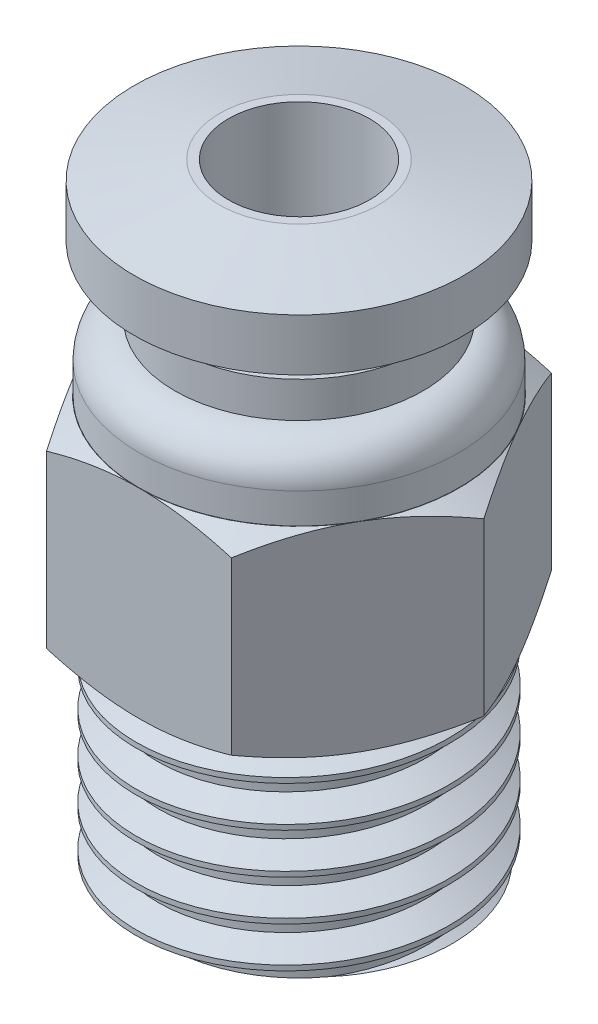
SolidWorks part; units mm, degrees
ref_plane "前视基准面" through (0, 0, 0) normal (0, 0, 1) x (1, 0, 0)
ref_plane "上视基准面" through (0, 0, 0) normal (0, 1, 0) x (1, 0, 0)
ref_plane "右视基准面" through (0, 0, 0) normal (1, 0, 0) x (0, 0, -1)
sketch "草图1" plane through (0, 0, 0) normal (0, 0, 1) x (1, 0, 0)
  line L0 (0, 0) -> (0, 6.9663) construction
  line L1 (-3.25, -7.6125) -> (-3.25, -4.0125)
  line L5 (-2.6208, 8.1221) -> (-3.82, 8.1221)
  line L6 (-3.82, 8.1221) -> (-3.82, 7.0221)
  line L7 (-3.82, 7.0221) -> (-4.92, 7.0221)
  line L8 (-4.92, 7.0221) -> (-4.92, 4.9875)
  line L9 (-4.92, 4.9875) -> (-5.69, 4.9875)
  line L10 (-5.69, 4.9875) -> (-5.69, -1.6125)
  line L11 (-5.69, -1.6125) -> (-4.14, -1.6125)
  line L12 (-4.14, -1.6125) -> (-4.14, -7.6125)
  line L13 (-4.14, -7.6125) -> (-3.25, -7.6125)
  line L14 (-2.6208, 8.1221) -> (-2.6208, 9.1221)
  line L15 (-2.6208, 9.1221) -> (-5.07, 9.1221)
  line L16 (-5.07, 9.1221) -> (-5.07, 10.7221)
  line L17 (-5.07, 10.7221) -> (-2.445, 11.2875)
  line L18 (-2.445, 11.2875) -> (-2.17, 11.2875)
  line L19 (-2.17, 11.2875) -> (-2.17, -3.2452)
  line L20 (-2.17, -3.2452) -> (-3.25, -4.0125)
  dimension "D1" = 18.9
  dimension "D2" = 8.28
  dimension "D3" = 5.69
  dimension "D4" = 3.25
  dimension "D5" = 3.6
  dimension "D6" = 2.17
  dimension "D7" = 5.07
  dimension "D8" = 1.6
  dimension "D9" = 1
  dimension "D10" = 3.82
  dimension "D11" = 2.1
  dimension "D12" = 4.92
  dimension "D13" = 6.6
  dimension "D14" = 6
revolve "旋转1" add sketch "草图1" angle 360 about L0
fillet "圆角1" radius 1.1 1 edges at (0, 7.0221, -4.92)
chamfer "倒角1" distance 0.76 angle 30 1 edges at (0, 4.9875, -5.69)
chamfer "倒角3" distance 0.9 distance2 1.55 1 edges at (0, -1.6125, -5.69)
ref_plane "基准面1" through (0, 4.5487, 0) normal (0, 1, 0) x (1, 0, 0)
sketch "草图3" plane through (0, 4.5487, 0) normal (0, 1, 0) x (1, 0, 0)
  line L1 (-5.69, 0) -> (-2.845, -4.9277)
  line L2 (-2.845, -4.9277) -> (2.845, -4.9277)
  line L3 (2.845, -4.9277) -> (5.69, 0)
  line L4 (5.69, 0) -> (2.845, 4.9277)
  line L5 (2.845, 4.9277) -> (-2.845, 4.9277)
  line L6 (-2.845, 4.9277) -> (-5.69, 0)
  circle A0 centre (0, 0) radius 4.9277 construction
  circle A1 centre (0, 0) radius 6.1809
extrude "切除-拉伸1" cut sketch "草图3" against normal blind 7 and the other way blind 2
thread "螺纹线1" pitch 1.25 start angle 0, offset 1, length 0, pitch 1.25, diameter 8.28
ref_plane "基准面2" through (-4.14, -0.6125, 0) normal (0, 0, 1) x (-1, 0, 0)
sketch "螺纹线轮廓1" plane through (-4.14, -0.6125, 0) normal (0, 0, 1) x (-1, 0, 0)
  line L0 (0, 0) -> (0, 1.25) construction
  line L1 (0, 0) -> (0.6766, 0.3906)
  line L2 (0.6766, 0.3906) -> (0.6766, 0.5469)
  line L3 (0.6766, 0.5469) -> (0, 0.9375)
  line L4 (0.6766, 0.4687) -> (0, 0.4687) construction
  line L11 (0, 0) -> (0, 0.9375)
  point P2 (0, 0)
  dimension "Pitch" = 1.25
  dimension "Profile_Angle" = 60
  dimension "Profile_Land" = 0.1562
  dimension "Profile_Height" = 0.6766
chamfer "倒角4" distance 0.2 angle 30 1 edges at (0, -7.6125, -3.25)
